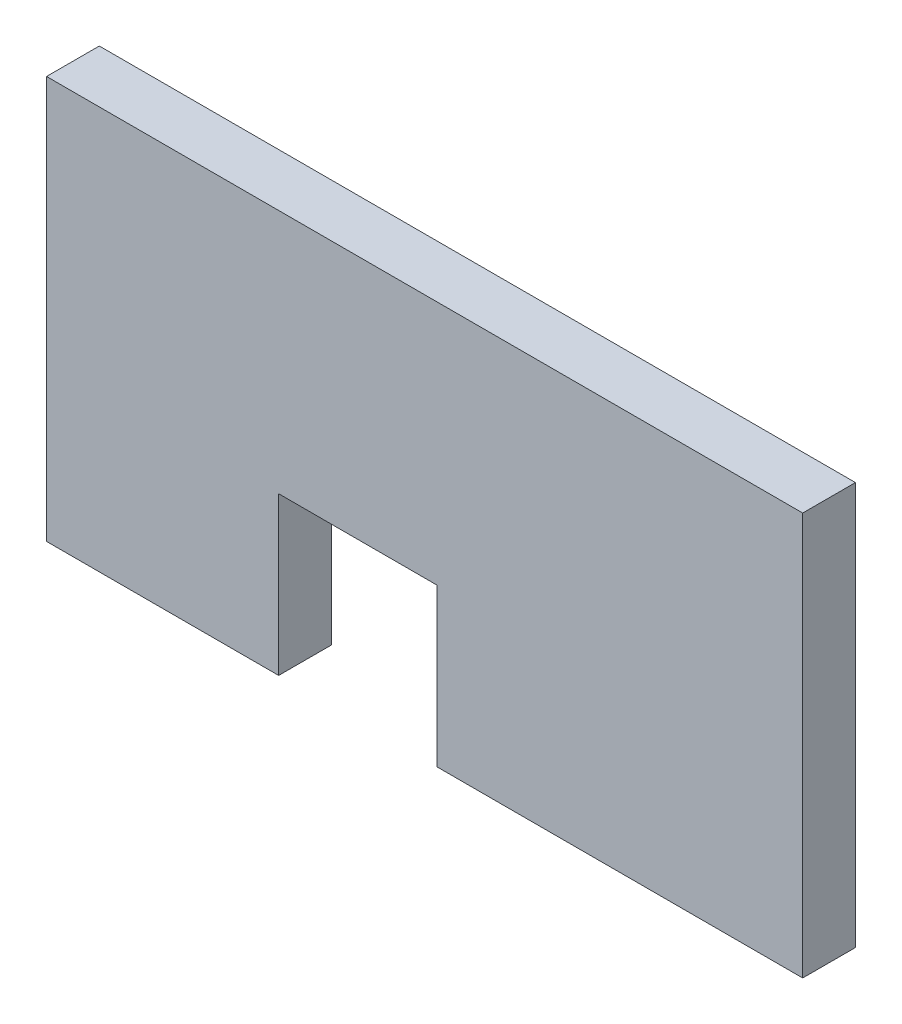
SolidWorks part; units mm, degrees
ref_plane "Front Plane" through (0, 0, 0) normal (0, 0, 1) x (1, 0, 0)
ref_plane "Top Plane" through (0, 0, 0) normal (0, 1, 0) x (1, 0, 0)
ref_plane "Right Plane" through (0, 0, 0) normal (1, 0, 0) x (0, 0, -1)
sketch "Sketch1" plane through (0, 0, 0) normal (0, 0, 1) x (1, 0, 0)
  line L0 (21.5, 33.35) -> (21.5, 15.05) construction
  line L1 (21.5, 37.95) -> (-21.5, 37.95)
  line L2 (21.5, 37.95) -> (21.5, 15.05)
  line L3 (21.5, 15.05) -> (0.7, 15.05)
  line L4 (-21.5, 37.95) -> (-21.5, 15.05)
  line L5 (-21.5, 33.35) -> (-21.5, 15.05) construction
  line L6 (32.157, 37.95) -> (-32.157, 37.95) construction
  line L7 (28.5, 15.05) -> (-28.5, 15.05) construction
  line L8 (0.7, 15.05) -> (0.7, 24) construction
  line L9 (0.7, 24) -> (-8.3, 24) construction
  line L10 (-8.3, 24) -> (-8.3, 15.05) construction
  line L11 (0.7, 15.05) -> (0.7, 24)
  line L12 (0.7, 24) -> (-8.3, 24)
  line L13 (-8.3, 24) -> (-8.3, 15.05)
  line L14 (-8.3, 15.05) -> (-21.5, 15.05)
sketch "Sketch2" plane through (0, 0, 0) normal (1, 0, 0) x (0, 0, -1)
  line L0 (0, 19.65) -> (0, 37.95) construction
  line L1 (0, 37.95) -> (-3, 37.95)
  line L2 (0, 37.95) -> (0, 15.05)
  line L3 (0, 15.05) -> (-3, 15.05)
  line L4 (-3, 37.95) -> (-3, 15.05)
  line L5 (-3, 19.65) -> (-3, 34.95) construction
  line L6 (-53.657, 15.05) -> (10.657, 15.05) construction
  line L7 (-50, 37.95) -> (7, 37.95) construction
extrude "Boss-Extrude1" add sketch "Sketch1" along normal up to vertex (3 mm away) up to point (0, 37.95, 3)
sketch "Sketch3" plane through (0, 0, 0) normal (0, 0, 1) x (1, 0, 0)
  line L0 (32.157, 37.95) -> (-32.157, 37.95) construction
  line L1 (21.5, 37.95) -> (-21.5, 37.95) construction
  line L2 (21.5, 37.95) -> (21.5, 15.05) construction
  line L3 (21.5, 15.05) -> (0.7, 15.05) construction
  line L4 (-21.5, 37.95) -> (-21.5, 15.05) construction
  line L5 (0.7, 15.05) -> (0.7, 24) construction
  line L6 (0.7, 24) -> (-8.3, 24) construction
  line L7 (-8.3, 24) -> (-8.3, 15.05) construction
  line L8 (0.7, 24) -> (-8.3, 24) construction
  line L9 (-8.3, 24) -> (-8.3, 15.05) construction
  line L10 (-3.0714, 28.186) -> (-3.0714, 26.5) construction
  line L11 (0.7, 15.05) -> (0.7, 24) construction
  line L12 (-8.3, 15.05) -> (-21.5, 15.05) construction
  line L13 (32.157, 26.5) -> (-32.157, 26.5) construction
  line L14 (32.157, 26.5) -> (-32.157, 26.5) construction
  line L15 (0, 15.05) -> (0, 37.95) construction
  line L16 (0, 15.05) -> (0, 37.95) construction
  line L17 (32.157, 33.35) -> (-32.157, 33.35) construction
  line L18 (32.157, 34.15) -> (-32.157, 34.15) construction
  line L19 (32.157, 37.15) -> (-32.157, 37.15) construction
  line L20 (21.5, 33.35) -> (-21.5, 33.35) construction
  line L21 (21.5, 34.15) -> (-21.5, 34.15) construction
  line L22 (21.5, 37.15) -> (-21.5, 37.15) construction
  line L23 (28.5, 19.65) -> (-28.5, 19.65) construction
  line L24 (28.5, 18.85) -> (0.7, 18.85) construction
  line L25 (-8.3, 18.85) -> (-28.5, 18.85) construction
  line L26 (-8.3, 15.85) -> (-28.5, 15.85) construction
  line L27 (28.5, 15.85) -> (0.7, 15.85) construction
  line L28 (21.5, 19.65) -> (0.7, 19.65) construction
  line L29 (21.5, 18.85) -> (0.7, 18.85) construction
  line L30 (-8.3, 18.85) -> (-21.5, 18.85) construction
  line L31 (-8.3, 15.85) -> (-21.5, 15.85) construction
  line L32 (21.5, 15.85) -> (0.7, 15.85) construction
  line L33 (-8.3, 19.65) -> (-21.5, 19.65) construction
  line L34 (-18.5, 15.05) -> (-18.5, 37.95) construction
  line L35 (21.5, 37.95) -> (18.5, 37.95)
  line L36 (21.5, 37.95) -> (21.5, 32.225)
  line L37 (21.5, 32.225) -> (18.5, 32.225)
  line L38 (18.5, 37.95) -> (18.5, 32.225)
  line L39 (21.5, 26.5) -> (18.5, 26.5)
  line L40 (21.5, 26.5) -> (21.5, 20.775)
  line L41 (21.5, 20.775) -> (18.5, 20.775)
  line L42 (18.5, 26.5) -> (18.5, 20.775)
  line L43 (18.5, 15.05) -> (18.5, 37.95) construction
  line L44 (18.5, 18.05) -> (18.5, 33.35) construction
  line L45 (-18.5, 33.35) -> (-18.5, 18.05) construction
  line L46 (20, 26.5) -> (20, 32.225) construction
  line L47 (3.0714, 15.05) -> (3.0714, 37.95) construction
  line L48 (9.2143, 15.05) -> (9.2143, 37.95) construction
  line L49 (15.3571, 15.05) -> (15.3571, 37.95) construction
  line L50 (21.5, 28.186) -> (15.3571, 28.186) construction
  line L51 (15.3571, 28.186) -> (9.2143, 28.186) construction
  line L52 (9.2143, 28.186) -> (3.0714, 28.186) construction
  line L53 (3.0714, 28.186) -> (-3.0714, 28.186) construction
  line L54 (-21.843, 31.9415) -> (-20.157, 31.9415) construction
  line L55 (-9.2143, 33.35) -> (-15.3571, 33.35)
  line L56 (9.2143, 33.35) -> (15.3571, 33.35)
  line L57 (9.2143, 33.35) -> (9.2143, 37.95)
  line L58 (9.2143, 37.95) -> (15.3571, 37.95)
  line L59 (15.3571, 33.35) -> (15.3571, 37.95)
  line L60 (3.0714, 33.35) -> (-3.0714, 33.35)
  line L61 (3.0714, 33.35) -> (3.0714, 37.95)
  line L62 (3.0714, 37.95) -> (-3.0714, 37.95)
  line L63 (-3.0714, 33.35) -> (-3.0714, 37.95)
  line L64 (9.2143, 19.65) -> (15.3571, 19.65)
  line L65 (9.2143, 19.65) -> (9.2143, 15.05)
  line L66 (9.2143, 15.05) -> (15.3571, 15.05)
  line L67 (15.3571, 19.65) -> (15.3571, 15.05)
  line L68 (0.7, 19.65) -> (-15.3571, 19.65)
  line L70 (0.7, 15.05) -> (-15.3571, 15.05)
  line L71 (-15.3571, 19.65) -> (-15.3571, 15.05)
  line L72 (-15.3571, 33.35) -> (-15.3571, 37.95)
  line L73 (-9.2143, 37.95) -> (-15.3571, 37.95)
  line L74 (-9.2143, 33.35) -> (-9.2143, 37.95)
  line L75 (-21.5, 37.95) -> (-18.5, 37.95)
  line L76 (-21.5, 37.95) -> (-21.5, 32.225)
  line L77 (-21.5, 32.225) -> (-18.5, 32.225)
  line L78 (-18.5, 37.95) -> (-18.5, 32.225)
  line L79 (-21.5, 26.5) -> (-18.5, 26.5)
  line L80 (-21.5, 26.5) -> (-21.5, 20.775)
  line L81 (-21.5, 20.775) -> (-18.5, 20.775)
  line L82 (-18.5, 26.5) -> (-18.5, 20.775)
  line L83 (0.7, 15.05) -> (0.7, 19.65)
